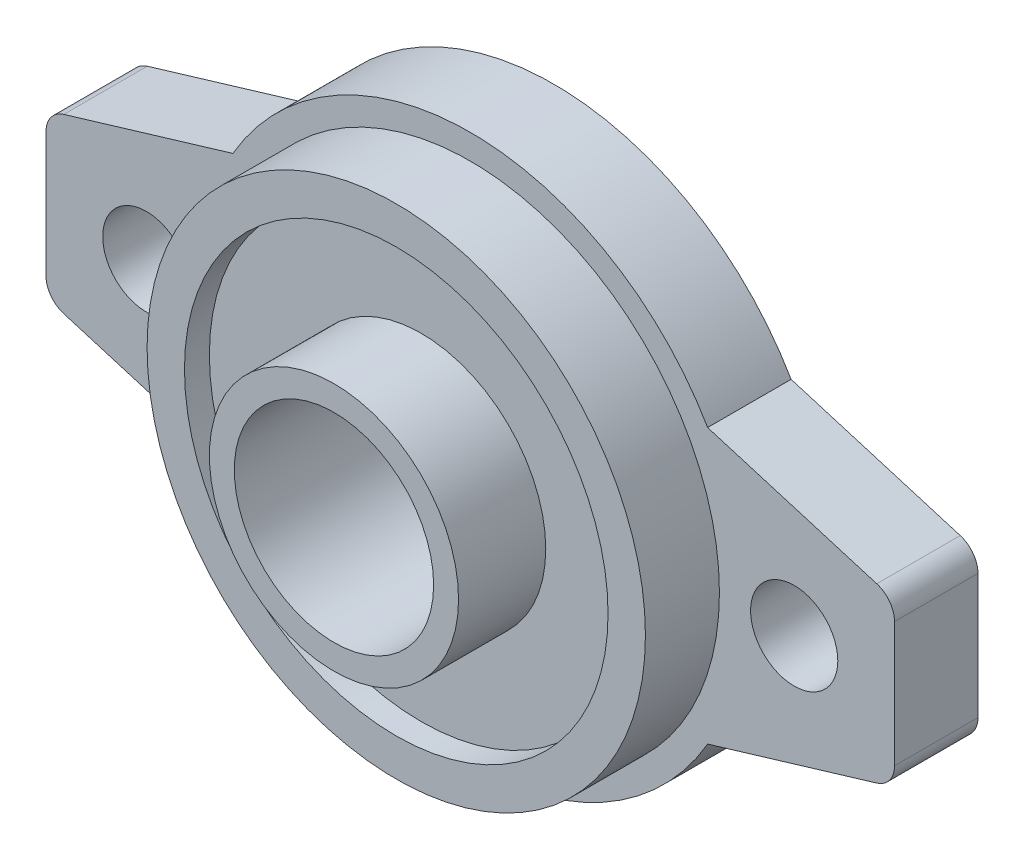
SolidWorks part; units mm, degrees
ref_plane "정면" through (0, 0, 0) normal (0, 0, 1) x (1, 0, 0)
ref_plane "윗면" through (0, 0, 0) normal (0, 1, 0) x (1, 0, 0)
ref_plane "우측면" through (0, 0, 0) normal (1, 0, 0) x (0, 0, -1)
sketch "스케치1" plane through (0, 0, 0) normal (0, 0, 1) x (1, 0, 0)
  line L0 (19.0526, 11) -> (34.0526, 6.5)
  line L4 (34.0526, 6.5) -> (34.0526, -6.5)
  line L5 (34.0526, -6.5) -> (19.0526, -11)
  line L6 (38.0288, 0) -> (-37.9012, 0) construction
  line L7 (0, 30.3127) -> (0, -31.0312) construction
  line L8 (-34.0526, -6.5) -> (-19.0526, -11)
  line L9 (-34.0526, 6.5) -> (-34.0526, -6.5)
  line L10 (-19.0526, 11) -> (-34.0526, 6.5)
  circle A0 centre (0, 0) radius 8
  circle A1 centre (0, 0) radius 20
  circle A2 centre (0, 0) radius 10
  arc A3 (19.0526, 11) -> (-19.0526, 11) centre (0, 0) ccw
  circle A4 centre (26, 0) radius 3.5
  circle A5 centre (0, 0) radius 22 construction
  circle A6 centre (-26, 0) radius 3.5
  circle A7 centre (0, 0) radius 17
  arc A8 (-19.0526, -11) -> (19.0526, -11) centre (0, 0) ccw
  dimension "D1" = 16
  dimension "D2" = 40
  dimension "D3" = 20
  dimension "D8" = 7
  dimension "D5" = 22
  dimension "D6" = 13
  dimension "D7" = 15
  dimension "D9" = 52
  dimension "D4" = 2
  dimension "D10" = 3
extrude "보스-돌출1" add sketch "스케치1" along normal blind 6.7 contours L8 A8 L5 L4 L0 A3 L10 L9 A6 A4 A1 | A1 A2 | A2 A0 | A7 region at (26.3196, 7.9734, 0) region at (-19.4343, 0, 0) region at (-9.7172, 0, 0)
extrude "보스-돌출2" add sketch "스케치1<4>" along normal blind 12.64 contours A1 A2 region at (-19.4343, 0, 0)
sketch "스케치1<4>" plane through (0, 0, 0) normal (0, 0, 1) x (1, 0, 0) same geometry as "스케치1"
extrude "보스-돌출3" add sketch "스케치1<5>" along normal offset from surface (10.64 mm away) 2 contours A7 A2 region at (-16.5192, 0, 0) up to face at (17, 0, 12.64)
sketch "스케치1<5>" plane through (0, 0, 0) normal (0, 0, 1) x (1, 0, 0) same geometry as "스케치1"
extrude "보스-돌출4" add sketch "스케치1<6>" along normal offset from surface (17.64 mm away) 7 contours A2 A0 region at (-9.7172, 0, 0) up to face at (10, 0, 10.64) offset beyond the face yes
sketch "스케치1<6>" plane through (0, 0, 0) normal (0, 0, 1) x (1, 0, 0) same geometry as "스케치1"
fillet "필렛1" radius 2 4 edges at (-34.0526, -6.5, 3.35) (-34.0526, 6.5, 3.35) (34.0526, -6.5, 3.35) (34.0526, 6.5, 3.35)
